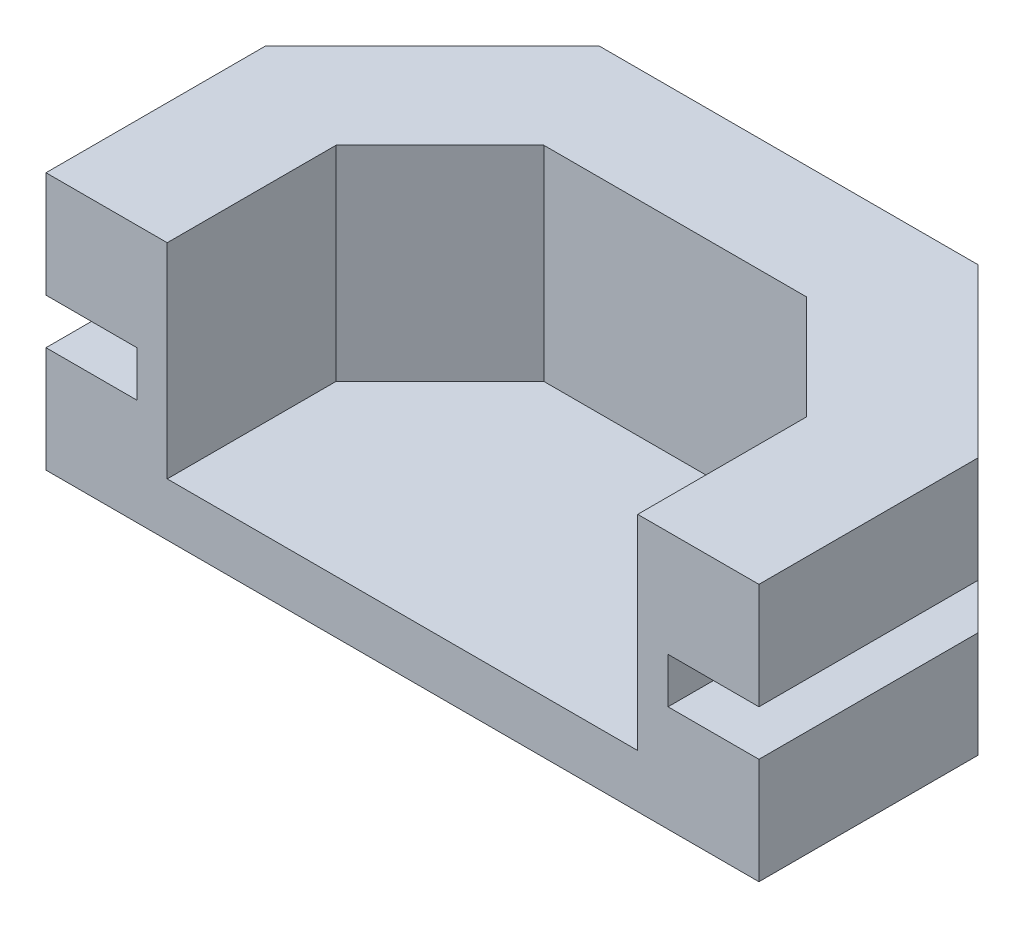
SolidWorks part; units mm, degrees
ref_plane "Front Plane" through (0, 0, 0) normal (0, 0, 1) x (1, 0, 0)
ref_plane "Top Plane" through (0, 0, 0) normal (0, 1, 0) x (1, 0, 0)
ref_plane "Right Plane" through (0, 0, 0) normal (1, 0, 0) x (0, 0, -1)
ref_plane "Motor Holder Bottom" through (0, -3.5, 0) normal (0, -1, 0) x (-1, 0, 0)
sketch "Sketch1" plane through (0, 0, 0) normal (0, 1, 0) x (1, 0, 0)
  line L5 (62.5266, -52.5) -> (68.5266, -52.5) construction
  line L6 (35, -33) -> (27.4734, -40.5266) construction
  line L7 (27.4734, -52.5) -> (21.4734, -52.5)
  line L10 (19.9734, -52.5) -> (27.4734, -52.5) construction
  line L13 (29.4734, -52.5) -> (60.5266, -52.5)
  line L16 (27.4734, -52.5) -> (27.4734, -40.5266)
  line L18 (60.5266, -52.5) -> (62.5266, -52.5)
  line L19 (55, -33) -> (62.5266, -40.5266)
  line L20 (27.4734, -40.5266) -> (35, -33)
  line L21 (62.5266, -40.5266) -> (62.5266, -52.5)
  line L22 (35, -33) -> (55, -33)
  line L23 (29.4734, -52.5) -> (29.4734, -41.3551)
  line L24 (35, -33) -> (55, -33) construction
  line L25 (29.4734, -41.3551) -> (36.3284, -34.5)
  line L26 (36.3284, -34.5) -> (53.6716, -34.5)
  line L27 (53.6716, -34.5) -> (60.5266, -41.3551)
  line L28 (60.5266, -41.3551) -> (60.5266, -52.5)
  line L29 (55, -33) -> (62.5266, -40.5266) construction
  line L30 (29.4734, -52.5) -> (27.4734, -52.5)
  line L31 (21.4734, -52.5) -> (21.4734, -38.0413)
  line L32 (21.4734, -38.0413) -> (32.5147, -27)
  line L33 (32.5147, -27) -> (57.4853, -27)
  line L34 (57.4853, -27) -> (68.5266, -38.0413)
  line L35 (68.5266, -38.0413) -> (68.5266, -52.5)
  line L36 (62.5266, -52.5) -> (68.5266, -52.5)
  dimension "D1" = 6
  dimension "D4" = 2
  dimension "D5" = 2
  dimension "D6" = 1.5
  dimension "D7" = 2
  dimension "D8" = 2
extrude "Boss-Extrude1" add sketch "Sketch1" along normal blind 10 and the other way blind 7 contours L16 | L16 L18 region at (24.4734, 0, 51.9648) region at (27.8745, 0, 46.5133)
extrude "Cut-Extrude1" cut sketch "Sketch1<3>" along normal up to surface (3 mm away)
sketch "Sketch1<3>" plane through (0, 0, 0) normal (0, 1, 0) x (1, 0, 0) same geometry as "Sketch1"
extrude "Boss-Extrude4" add sketch "Sketch1<5>" along normal up to surface (-3.5 mm away) from surface contours L28 L27 L26 L25 L23 L13 region at (45, 0, 44.1163) up to plane "Motor Holder Bottom" starting at face at (45, -7, 40.9827)
sketch "Sketch1<5>" plane through (0, 0, 0) normal (0, 1, 0) x (1, 0, 0) same geometry as "Sketch1"
